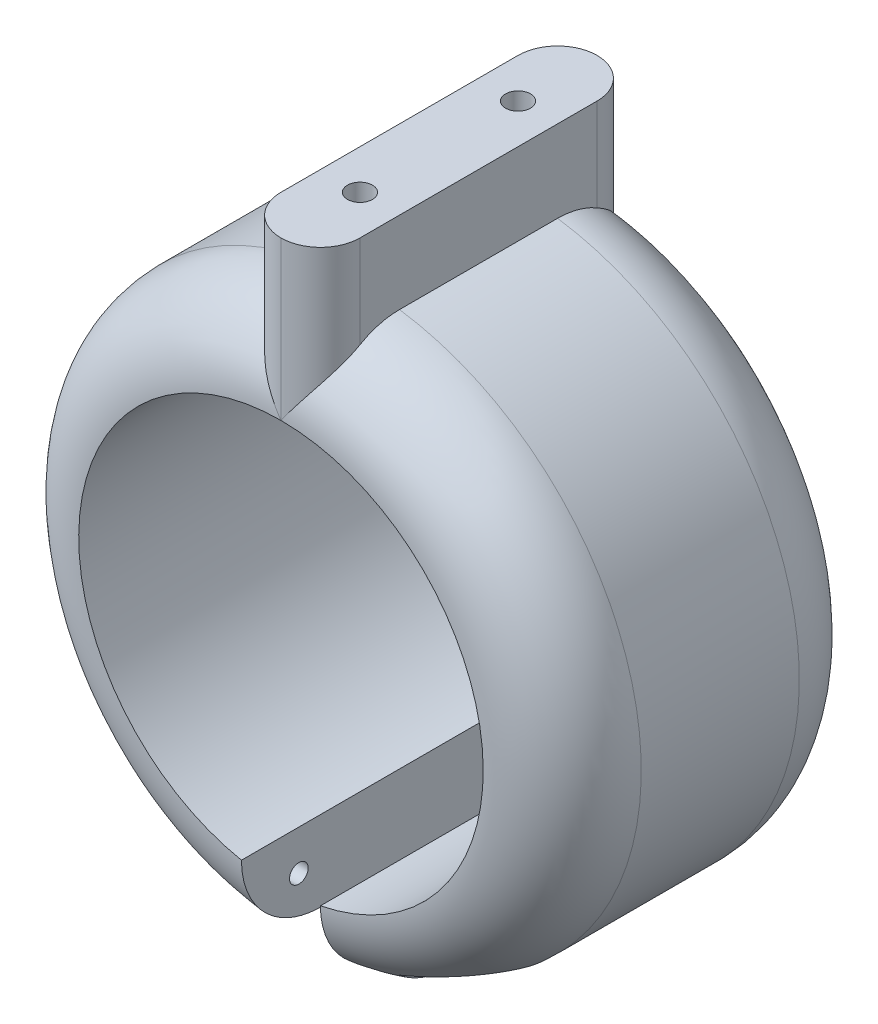
SolidWorks part; units mm, degrees
material "ABS"
ref_plane "Front Plane" through (0, 0, 0) normal (0, 0, 1) x (1, 0, 0)
ref_plane "Top Plane" through (0, 0, 0) normal (0, 1, 0) x (1, 0, 0)
ref_plane "Right Plane" through (0, 0, 0) normal (1, 0, 0) x (0, 0, -1)
sketch "Sketch3" plane through (0, 0, 0) normal (0, 0, 1) x (1, 0, 0)
  line L2 (-6.35, 32.5) -> (6.35, 32.5) construction
  line L3 (0, 32.5) -> (0, 0) construction
  line L7 (-45.2, 0) -> (-32.5, 0)
  line L8 (-6.35, 32.5) -> (-6.35, 44.7517) construction
  line L9 (6.35, 32.5) -> (6.35, 44.7517) construction
  line L11 (-6.35, 44.7517) -> (-6.35, 57.9)
  line L12 (-6.35, 57.9) -> (6.35, 57.9)
  line L13 (6.35, 57.9) -> (6.35, 44.7517)
  line L14 (0, 32.5) -> (0, 45.2) construction
  circle A0 centre (0, 0) radius 32.5
  circle A2 centre (0, 0) radius 45.2
  point P5 (0, 32.5)
  dimension "D1" = 65
  dimension "D2" = 32.5
  dimension "D3" = 12.7
  dimension "D4" = 12.7
  dimension "D5" = 12.7
extrude "Boss-Extrude2" add sketch "Sketch3" along normal mid plane 50.8 contours A0 L7 | L7 A0 | L11 A2 L13 L12 region at (-33.1671, 28.7931, 0) region at (0, 51.4747, 0)
sketch "Sketch9" plane through (0, 57.9, 0) normal (0, 1, 0) x (1, 0, 0)
  line L0 (0, -25.4) -> (0, 25.4) construction
  line L1 (0, -12.7) -> (0, 12.7) construction
  circle A0 centre (0, 12.7) radius 2
  circle A1 centre (0, -12.7) radius 2
  point P8 (0, 0)
  dimension "D2" = 4
  dimension "D1" = 25.4
extrude "Cut-Extrude7" cut sketch "Sketch9" against normal blind 36.068
sketch "Sketch10" plane through (0, 0, 0) normal (0, 1, 0) x (1, 0, 0)
  line L0 (0, 12.7) -> (0, -12.7) construction
  line L1 (6.35, 12.7) -> (6.35, -12.7)
  line L2 (-6.35, 12.7) -> (-6.35, -12.7)
  arc A0 (6.35, 12.7) -> (-6.35, 12.7) centre (0, 12.7) ccw
  arc A1 (-6.35, -12.7) -> (6.35, -12.7) centre (0, -12.7) ccw
  point P2 (0, 0)
  dimension "D1" = 12.7
extrude "Cut-Extrude8" cut sketch "Sketch10" along normal blind 36.068
sketch "Sketch11" plane through (0, 0, 25.4) normal (0, 0, 1) x (1, 0, 0)
  line L0 (0, -32.5) -> (0, -45.2) construction
  line L1 (0, -32.5) -> (0, -26.3189) construction
  line L2 (-6.35, -45.2) -> (6.35, -45.2)
  line L3 (-6.35, -26.3189) -> (6.35, -26.3189)
  line L4 (-6.35, -26.3189) -> (-6.35, -45.2)
  line L5 (6.35, -26.3189) -> (6.35, -45.2)
  circle A0 centre (0, 0) radius 32.5 construction
  arc A1 (-6.35, 44.7517) -> (6.35, 44.7517) centre (0, 0) ccw construction
  point P12 (0, -45.2)
  point P15 (0, -26.3189)
  dimension "D1" = 12.7
extrude "Cut-Extrude9" cut sketch "Sketch11" against normal up to surface (50.8 mm away) up to face at (32.5, 0, -25.4)
ref_plane "Plane1" through (55.3851, 0, 0) normal (1, 0, 0) x (0, 0, -1)
sketch "Sketch12" plane through (55.3851, 0, 0) normal (1, 0, 0) x (0, 0, -1)
  line L0 (0, -31.8736) -> (0, -44.7517) construction
  line L1 (-16.1723, -38.3127) -> (16.1723, -38.3127) construction
  line L2 (-16.1723, -33.5502) -> (16.1723, -33.5502)
  line L3 (-16.1723, -43.0752) -> (16.1723, -43.0752)
  line L4 (25.4, -31.8736) -> (-25.4, -31.8736)
  line L5 (-25.4, -31.8736) -> (-25.4, -44.7517)
  line L6 (-25.4, -44.7517) -> (25.4, -44.7517)
  line L7 (25.4, -44.7517) -> (25.4, -31.8736)
  line L8 (25.4, -31.8736) -> (-25.4, -31.8736) construction
  line L9 (-25.4, -31.8736) -> (-25.4, -44.7517) construction
  line L10 (-25.4, -44.7517) -> (25.4, -44.7517) construction
  line L11 (25.4, -44.7517) -> (25.4, -31.8736) construction
  arc A0 (-16.1723, -33.5502) -> (-16.1723, -43.0752) centre (-16.1723, -38.3127) ccw
  arc A1 (16.1723, -43.0752) -> (16.1723, -33.5502) centre (16.1723, -38.3127) ccw
  circle A2 centre (-16.1723, -38.3127) radius 1.5
  circle A3 centre (16.1723, -38.3127) radius 1.5
  point P8 (0, -38.3127)
  dimension "D3" = 3
  dimension "D2" = 9.525
  dimension "D1" = 0
extrude "Cut-Extrude10" cut sketch "Sketch12" against normal blind 41.148 contours L3 A1 L2 A0 A3 A2 | A3 | A2 region at (55.3851, -38.3127, 0) region at (55.3851, -38.3127, 16.1723) region at (55.3851, -38.3127, -16.1723)
extrude "Cut-Extrude11" cut sketch "Sketch12<4>" against normal blind 128.778 contours A2 | A3 region at (55.3851, -38.3127, 16.1723) region at (55.3851, -38.3127, -16.1723)
sketch "Sketch12<4>" plane through (55.3851, 0, 0) normal (1, 0, 0) x (0, 0, -1) same geometry as "Sketch12"
mirror "Mirror1" about plane through (0, 0, 0) normal (1, 0, 0) of "Cut-Extrude10"
fillet "Fillet4" radius 12.7 1 edges at (-45.2, 0, 25.4)
fillet "Fillet5" radius 12.7 1 edges at (45.2, 0, 25.4)
fillet "Fillet6" radius 6.35 2 edges at (6.35, 44.8868, 25.4) (-6.35, 44.8868, 25.4)
fillet "Fillet7" radius 12.7 1 edges at (45.2, 0, -25.4)
fillet "Fillet8" radius 12.7 1 edges at (-45.2, 0, -25.4)
fillet "Fillet9" radius 6.35 2 edges at (-6.35, 44.8868, -25.4) (6.35, 44.8868, -25.4)
